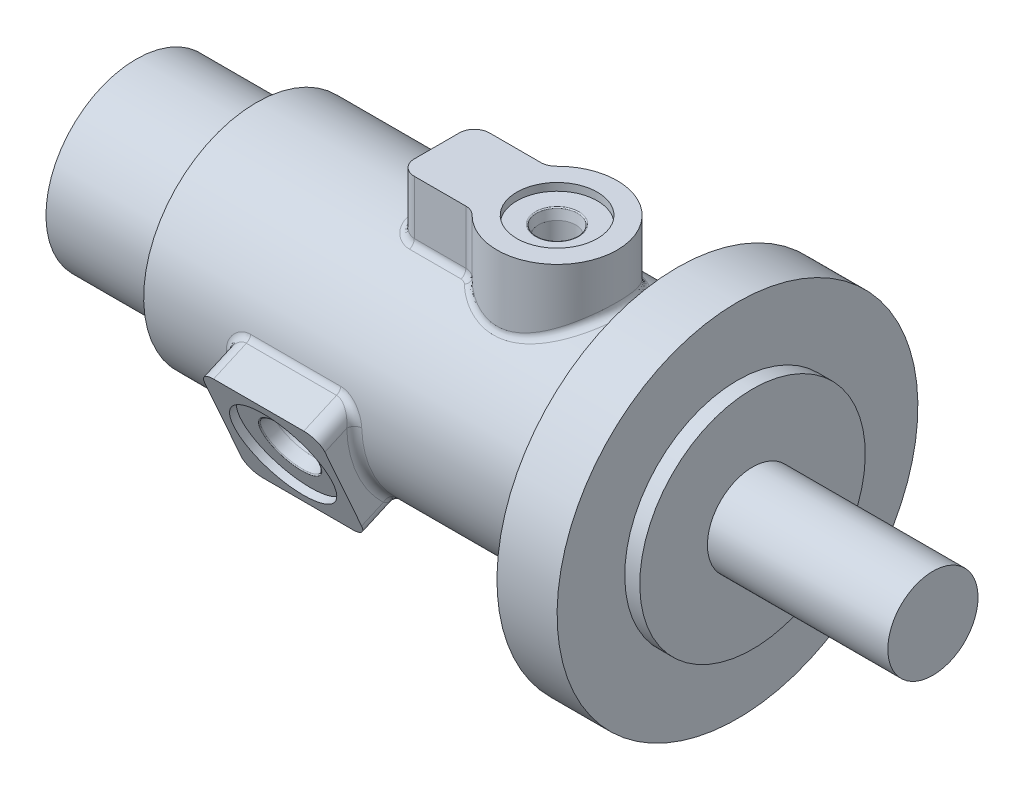
SolidWorks part; units mm, degrees
ref_plane "Front" through (0, 0, 0) normal (0, 0, 1) x (1, 0, 0)
ref_plane "Top" through (0, 0, 0) normal (0, 1, 0) x (1, 0, 0)
ref_plane "Right" through (0, 0, 0) normal (1, 0, 0) x (0, 0, -1)
sketch "Sketch1" plane through (0, 0, 0) normal (0, 0, 1) x (1, 0, 0)
  line L0 (42.975, 0) -> (28.575, 0) construction
  line L1 (0, 0) -> (0, 23.8125)
  line L2 (0, 23.8125) -> (-3.175, 23.8125)
  line L3 (-3.175, 23.8125) -> (-3.175, 38.1)
  line L4 (-3.175, 38.1) -> (-15.875, 38.1)
  line L5 (-15.875, 38.1) -> (-15.875, 23.8125)
  line L6 (-15.875, 23.8125) -> (-104.775, 23.8125)
  line L7 (-104.775, 23.8125) -> (-104.775, 19.05)
  line L8 (-104.775, 19.05) -> (-130.175, 19.05)
  line L9 (-130.175, 19.05) -> (-130.175, 0)
  line L10 (-130.175, 0) -> (0, 0)
  line L14 (0, 0) -> (-120.4051, 0) construction
  dimension "D1" = 47.625
  dimension "D2" = 3.175
  dimension "D3" = 12.7
  dimension "D4" = 76.2
  dimension "D5" = 127
  dimension "D6" = 25.4
  dimension "D7" = 38.1
revolve "case" add sketch "Sketch1" angle 360 about L0
sketch "Sketch2" plane through (0, 0, 0) normal (0, 1, 0) x (1, 0, 0)
  line L0 (0, 0) -> (-124.2367, 0) construction
  line L1 (-3.175, -38.1) -> (-3.175, 38.1) construction
  line L2 (-66.675, 7.9375) -> (-51.1889, 7.9375)
  line L3 (-66.675, -7.9375) -> (-51.1889, -7.9375)
  line L4 (-66.675, 7.9375) -> (-66.675, -7.9375)
  arc A1 (-51.1889, -7.9375) -> (-51.1889, 7.9375) centre (-41.275, 0) ccw
  dimension "D2" = 12.7
  dimension "D3" = 25.4
  dimension "D1" = 38.1
  dimension "D4" = 7.9375
extrude "upper" add sketch "Sketch2" along normal blind 34.925
ref_plane "angle front" through (0, 0, 0) normal (0, -0.4067, 0.9135) x (1, 0, 0)
sketch "Sketch3" plane through (0, 0, 0) normal (0, -0.4067, 0.9135) x (1, 0, 0)
  line L1 (-85.725, -12.7) -> (-60.325, -12.7)
  line L2 (-85.725, -12.7) -> (-85.725, 12.7)
  line L3 (-85.725, 12.7) -> (-60.325, 12.7)
  line L4 (-60.325, -12.7) -> (-60.325, 12.7)
  line L6 (-15.875, 38.1) -> (-15.875, -38.1) construction
  line L7 (-85.725, 0) -> (-60.325, 0) construction
  line L8 (42.975, 0) -> (28.575, 0) construction
  dimension "D1" = 44.45
  dimension "D2" = 25.4
  dimension "D3" = 25.4
extrude "side" add sketch "Sketch3" along normal blind 28.575
fillet "Fillet1" radius 3.175 8 edges at (-66.675, 28.6878, -7.9375) (-51.1889, 28.6878, -7.9375) (-51.1889, 28.6878, 7.9375) (-66.675, 28.6878, 7.9375) (-60.325, 1.6943, 27.4187) (-85.725, 1.6943, 27.4187) (-85.725, -21.5097, 17.0876) (-60.325, -21.5097, 17.0876)
fillet "Fillet2" radius 1.5875 16 edges at (-84.3216, -19.4359, 13.7579) (-73.025, -19.795, 13.2361) (-61.1589, -19.1035, 14.2159) (-60.325, -9.6854, 21.7538) (-85.725, -9.6854, 21.7538) (-61.7284, 2.7811, 23.6495) (-84.8911, 2.2182, 23.709) (-66.675, 23.8125, 0) (-65.9498, 22.8262, -6.7821) (-58.056, 22.4506, -7.9375) (-51.6109, 22.3927, -8.0995) (-28.7569, 23.716, -2.1418) (-65.4072, 22.6657, 7.3009) (-58.056, 22.4506, 7.9375) (-51.1647, 22.3241, 8.2866) (-73.025, 3.4091, 23.5672)
sketch "Sketch4" plane through (0, 0, 0) normal (1, 0, 0) x (0, 0, -1)
  circle A0 centre (0, 0) radius 9.525
  dimension "D1" = 19.05
extrude "shaft" add sketch "Sketch4" along normal blind 38.1
sketch "Sketch21" plane through (-39.3884, 34.925, -1.6405) normal (0, -1, 0) x (1, 0, 0)
  line L0 (0.5765, 3.6439) -> (-4.3497, -0.363) construction
  line L1 (3.175, 0) -> (-0.8319, 4.9262) construction
  circle A0 centre (-1.8866, 1.6405) radius 12.7 construction
  point P5 (-1.8866, 1.6405)
  dimension "D3" = 6.35
ref_plane "Plane1" through (-41.275, 34.925, 0) normal (-0.7758, 0, -0.631) x (-0.631, 0, 0.7758)
sketch "Port Sketch" plane through (-39.1423, 34.925, -2.622) normal (0.7758, 0, 0.631) x (-0.631, 0, 0.7758)
  line L0 (3.3798, 0) -> (3.3798, 45.0293) construction
  line L1 (3.3798, 15.6756) -> (6.8342, 13.6)
  line L2 (6.8342, 13.6) -> (6.8342, 11.6)
  line L3 (6.8342, 11.6) -> (7.3485, 11.6)
  line L4 (7.3485, 11.6) -> (7.3485, 3.6542)
  line L5 (7.3485, 3.6542) -> (7.3027, 3.7)
  line L6 (7.3027, 3.7) -> (7.7063, 1.8012)
  line L7 (7.9548, 1.6) -> (11.8798, 1.6)
  line L8 (11.8798, 1.6) -> (11.8798, 0)
  line L10 (11.8798, 0) -> (3.3798, 0)
  line L11 (3.3798, 0) -> (3.3798, 15.6756)
  line L12 (-0.5432, 3.7) -> (-0.9468, 1.8012) construction
  line L13 (-0.589, 3.6542) -> (-0.5432, 3.7) construction
  line L14 (3.3798, 15.6756) -> (-0.0746, 13.6) construction
  arc A0 (7.7063, 1.8012) -> (7.9548, 1.6) centre (7.9548, 1.854) ccw
  dimension "D1" = 0.254
  dimension "Countersink angle" = 118
  dimension "D3" = 45
  dimension "TapDrillDia" = 6.9088
  dimension "D5" = 9.15
  dimension "ThdMjr" = 7.9375
  dimension "SpotDia" = 17
  dimension "L3" = 1.6
  dimension "L1" = 2.1
  dimension "ThdDp" = 10
  dimension "TapDrillDp" = 12
  dimension "K" = 12
revolve "SAE Port" cut sketch "Port Sketch" angle 360 about L0
other "sae j1926-1 (circular face)<1>"
sketch "Sketch23" plane through (-73.284, -12.0322, 25.9222) normal (0, 0.4067, -0.9135) x (-1, 0, 0)
  line L0 (-3.434, 0.4484) -> (2.916, 0.4484) construction
  line L1 (-0.259, 3.6234) -> (-0.259, -2.7266) construction
  line L2 (-12.959, 9.9734) -> (-12.959, -9.0766) construction
  line L3 (9.266, 13.1484) -> (-9.784, 13.1484) construction
  point P4 (-0.259, 0.4484)
  dimension "Locating dim1" = 12.7
  dimension "Locating dim2" = 12.7
  dimension "D3" = 6.35
ref_plane "Plane12" through (-73.025, -11.6225, 26.1046) normal (-1, 0, 0) x (0, 0, 1)
sketch "Port Sketch2" plane through (-73.025, -8.8295, 27.3481) normal (1, 0, 0) x (0, -0.9135, -0.4067)
  line L0 (3.0573, 0) -> (3.0573, 45.0293) construction
  line L1 (3.0573, 18.5806) -> (8.0179, 15.6)
  line L2 (8.0179, 15.6) -> (8.0179, 13.1)
  line L3 (8.0179, 13.1) -> (8.6136, 13.1)
  line L4 (8.6136, 13.1) -> (8.6136, 4.1104)
  line L5 (8.6136, 4.1104) -> (8.524, 4.2)
  line L6 (8.524, 4.2) -> (9.0339, 1.8012)
  line L7 (9.2823, 1.6) -> (13.5573, 1.6)
  line L8 (13.5573, 1.6) -> (13.5573, 0)
  line L10 (13.5573, 0) -> (3.0573, 0)
  line L11 (3.0573, 0) -> (3.0573, 18.5806)
  line L12 (-2.4093, 4.2) -> (-2.9192, 1.8012) construction
  line L13 (-2.4989, 4.1104) -> (-2.4093, 4.2) construction
  line L14 (3.0573, 18.5806) -> (-1.9033, 15.6) construction
  arc A0 (9.0339, 1.8012) -> (9.2823, 1.6) centre (9.2823, 1.854) ccw
  dimension "D1" = 0.254
  dimension "Countersink angle" = 118
  dimension "D3" = 45
  dimension "TapDrillDia" = 9.9212
  dimension "D5" = 12.45
  dimension "ThdMjr" = 11.1125
  dimension "SpotDia" = 21
  dimension "L3" = 1.6
  dimension "L1" = 2.6
  dimension "ThdDp" = 11.5
  dimension "TapDrillDp" = 14
  dimension "K" = 12
revolve "SAE Port2" cut sketch "Port Sketch2" angle 360 about L0
other "sae j1926-1 (rectangular face)<1>"
sketch "Sketch24" [suppressed] plane through (38.1, -0.8764, -5.6241) normal (1, 0, 0) x (0, 0, -1)
  line L0 (-5.6241, 10.4014) -> (-5.6241, 0.8764) construction
  line L1 (-5.6241, 0.8764) -> (-5.6241, 10.4014) construction
  circle A0 centre (-5.6241, 0.8764) radius 9.525 construction
  circle A2 centre (-5.6241, 0.8764) radius 9.525
  dimension "Angle from vertical" = 360
ref_plane "Plane13" [suppressed] through (38.1, 9.525, 0) normal (0, -1, 0) x (-1, 0, 0)
sketch "Sketch31" [suppressed] plane through (38.1, 9.525, 2.812) normal (0, -1, 0) x (1, 0, 0)
  line L0 (-6.35, -2.812) -> (-25.4, -2.812) construction
  line L1 (-6.35, -0.4308) -> (-25.4, -0.4308)
  line L2 (-6.35, -5.1933) -> (-25.4, -5.1933)
  arc A0 (-6.35, -0.4308) -> (-6.35, -5.1933) centre (-6.35, -2.812) cw
  arc A1 (-25.4, -0.4308) -> (-25.4, -5.1933) centre (-25.4, -2.812) ccw
  dimension "Keyway width" = 4.7625
  dimension "Distance from end face" = 6.35
  dimension "Length of slot" = 19.05
extrude "Cut-Extrude1" [suppressed] cut sketch "Sketch31" along normal blind 1.9177
other "rectangular keyseat<1>" [suppressed]
